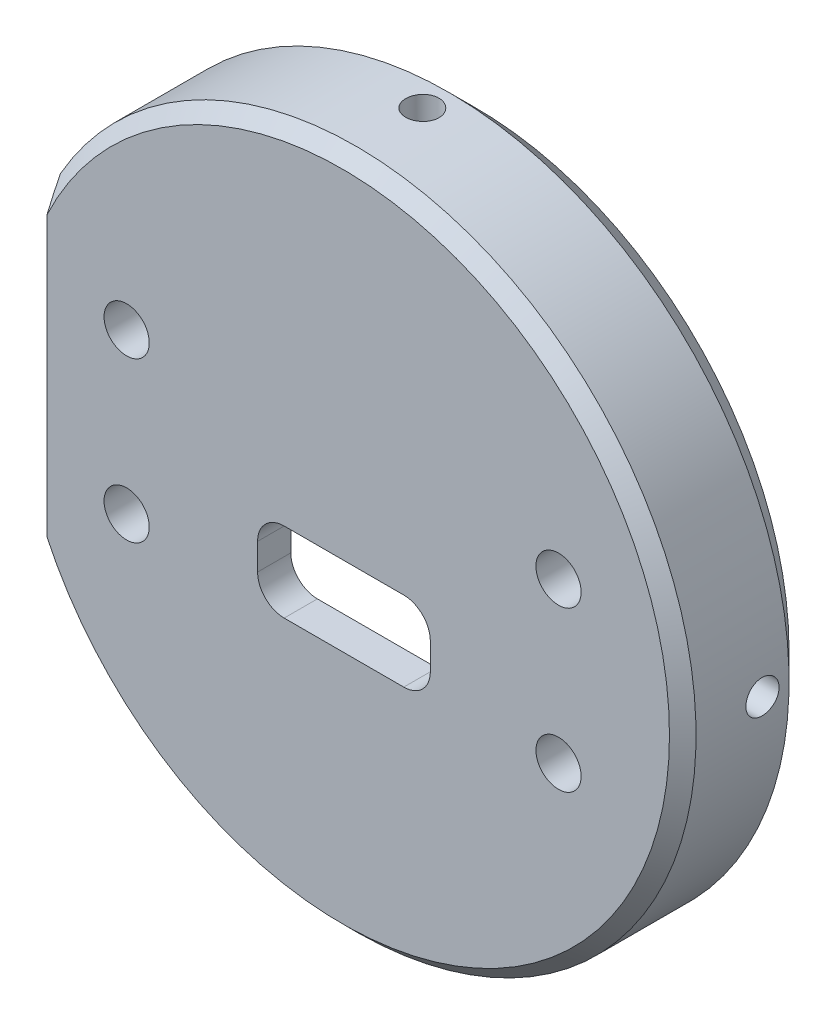
SolidWorks part; units mm, degrees
material "Сплав 2024"
ref_plane "Спереди" through (0, 0, 0) normal (0, 0, 1) x (1, 0, 0)
ref_plane "Сверху" through (0, 0, 0) normal (0, 1, 0) x (1, 0, 0)
ref_plane "Справа" through (0, 0, 0) normal (1, 0, 0) x (0, 0, -1)
sketch "Эскиз1" plane through (0, 0, 0) normal (0, 0, 1) x (1, 0, 0)
  circle A0 centre (0, 0) radius 25.6
  dimension "D1" = 51.2
extrude "Бобышка-Вытянуть1" add sketch "Эскиз1" along normal blind 10
chamfer "Фаска1" distance 2 angle 45 1 edges at (25.6, 0, 0)
sketch "Эскиз2" plane through (0, 0, 10) normal (0, 0, 1) x (1, 0, 0)
  line L0 (-22.25, -12.6609) -> (-22.25, 12.6609)
  line L1 (-22.25, -12.5) -> (-22.25, -10) construction
  circle A0 centre (0, 0) radius 25.6 construction
  arc A1 (-22.25, 12.6609) -> (-22.25, -12.6609) centre (0, 0) ccw
  circle A2 centre (0, 0) radius 25.6 construction
extrude "Вырез-Вытянуть1" cut sketch "Эскиз2" against normal blind 2.5
sketch "Эскиз3" plane through (0, 0, 0) normal (0, 0, -1) x (-1, 0, 0)
  circle A0 centre (0, 0) radius 23.2
  dimension "D1" = 46.4
extrude "Вырез-Вытянуть2" cut sketch "Эскиз3" against normal offset from surface (7.5 mm away) 2.5 up to face at (1.675, 0, 10)
ref_plane "Плоскость1" through (0, -12.6609, 0) normal (0, 1, 0) x (1, 0, 0)
sketch "Эскиз5" plane through (0, 0, 0) normal (0, 0, -1) x (-1, 0, 0)
  line L0 (22.25, 6.571) -> (22.25, -6.571) construction
  line L1 (17.5672, 12.6609) -> (26.9328, 12.6609)
  line L2 (17.5672, 12.6609) -> (17.5672, -12.6609)
  line L3 (17.5672, -12.6609) -> (26.9328, -12.6609)
  line L4 (26.9328, 12.6609) -> (26.9328, -12.6609)
  line L5 (17.5672, 12.6609) -> (26.9328, -12.6609) construction
  line L6 (17.5672, -12.6609) -> (26.9328, 12.6609) construction
  line L7 (1.375, -12.6609) -> (-1.375, -12.6609) construction
  point P0 (22.25, 0)
extrude "Вырез-Вытянуть3" cut sketch "Эскиз5" against normal up to surface (7.5 mm away) up to face at (0.475, 0, 7.5)
fillet "Скругление2" radius 4 2 edges at (-19.4407, 12.6609, 3.75) (-19.4407, -12.6609, 3.75)
chamfer "Фаска2" distance 1 angle 45 1 edges at (25.6, 0, 10)
sketch "Эскиз6" plane through (0, 0, 7.5) normal (0, 0, -1) x (-1, 0, 0)
  line L1 (-6.6034, -0.86) -> (6.3966, -0.86)
  line L2 (-6.6034, -0.86) -> (-6.6034, -6.86)
  line L3 (-6.6034, -6.86) -> (6.3966, -6.86)
  line L4 (6.3966, -0.86) -> (6.3966, -6.86)
  line L5 (-6.6034, -0.86) -> (6.3966, -6.86) construction
  line L6 (-6.6034, -6.86) -> (6.3966, -0.86) construction
  point P0 (-0.1034, -3.86)
  dimension "D1" = 6
  dimension "D2" = 13
extrude "Вырез-Вытянуть4" cut sketch "Эскиз6" against normal up to next
fillet "Скругление3" radius 2 4 edges at (-6.3966, -0.86, 8.75) (-6.3966, -6.86, 8.75) (6.6034, -6.86, 8.75) (6.6034, -0.86, 8.75)
sketch "Эскиз7" plane through (0, 0, 7.5) normal (0, 0, -1) x (-1, 0, 0)
  line L0 (-22.25, -6) -> (18.9231, -6) construction
  line L1 (-22.25, -10) -> (-22.25, 10) construction
  line L2 (-22.25, 6) -> (18.9231, 6) construction
  line L3 (-22.25, -10) -> (-9.25, -10) construction
  line L4 (-22.25, 10) -> (-9.25, 10) construction
  line L5 (-16.25, -6) -> (-16.25, 6) construction
  line L6 (16.25, -6) -> (16.25, 6) construction
  line L7 (22.25, -10.4927) -> (22.25, 10.4927) construction
  dimension "D1" = 4
  dimension "D2" = 4
  dimension "D3" = 6
  dimension "D4" = 6
hole_wizard "Отверстие с зазором M31" positions "Эскиз9" profile "Эскиз8" hole size "M3" standard "Ansi Metric" end condition up to next
sketch "Эскиз9" plane through (0, 0, 7.5) normal (0, 0, -1) x (-1, 0, 0)
  point P0 (16.25, -6)
  point P3 (16.25, 6)
  point P6 (-16.25, 6)
  point P9 (-16.25, -6)
sketch "Эскиз8" plane through (-16.25, -6, 7.5) normal (1, 0, 0) x (0, 1, 0)
  line L0 (0, 0) -> (0, 2.5)
  line L1 (0, 2.5) -> (1.7, 2.5)
  line L2 (1.7, 2.5) -> (1.7, 0)
  line L5 (1.7, 0) -> (0, 0)
  line L11 (0, -6.35) -> (0, 107.95) construction
  dimension "Диаметр сквозного отверстия" = 3.4
  dimension "Глубина сквозного отверстия" = 2.5
ref_plane "Плоскость2" through (25.6, 0, 0) normal (1, 0, 0) x (0, 0, -1)
sketch "Эскиз10" plane through (25.6, 0, 0) normal (1, 0, 0) x (0, 0, -1)
  line L0 (0, 0) -> (-6.6441, 0) construction
  line L1 (0, -23.6) -> (0, 23.6) construction
  point P3 (-4, 0)
  dimension "D1" = 4
hole_wizard "Отверстие обработанное метчиком M3x0.51" positions "Эскиз12" profile "Эскиз11" tap size "M3x0.5" standard "Ansi Metric" end condition up to next
sketch "Эскиз12" plane through (25.6, 0, 0) normal (1, 0, 0) x (0, 0, -1)
  point P0 (-4, 0)
sketch "Эскиз11" plane through (25.6, 0, 4) normal (0, 1, 0) x (0, 0, -1)
  line L0 (0, 0) -> (0, 2.4)
  line L1 (0, 2.4) -> (1.25, 2.4)
  line L2 (1.25, 2.4) -> (1.25, 0)
  line L5 (1.25, 0) -> (0, 0)
  line L11 (0, -6.35) -> (0, 107.95) construction
  dimension "Диаметр резьбы" = 2.5
  dimension "Глубина проходного сверла" = 2.4
ref_plane "Плоскость3" through (0, 25.6, 0) normal (0, 1, 0) x (1, 0, 0)
sketch "Эскиз13" plane through (0, 25.6, 0) normal (0, 1, 0) x (1, 0, 0)
  line L0 (0, 0) -> (0, -8.4626) construction
  line L2 (23.2, 0) -> (-18.3383, 0) construction
  point P3 (0, -4)
  dimension "D1" = 4
hole_wizard "Отверстие обработанное метчиком M3x0.52" positions "Эскиз15" profile "Эскиз14" tap size "M3x0.5" standard "Ansi Metric" end condition through all
sketch "Эскиз15" plane through (0, 25.6, 0) normal (0, 1, 0) x (1, 0, 0)
  point P0 (0, -4)
sketch "Эскиз14" plane through (0, 25.6, 4) normal (1, 0, 0) x (0, 0, 1)
  line L0 (0, 0) -> (0, 51.2)
  line L1 (0, 51.2) -> (1.25, 51.2)
  line L2 (1.25, 51.2) -> (1.25, 0)
  line L5 (1.25, 0) -> (0, 0)
  line L11 (0, -6.35) -> (0, 107.95) construction
  dimension "Диаметр резьбы" = 2.5
  dimension "Глубина проходного сверла" = 51.2
